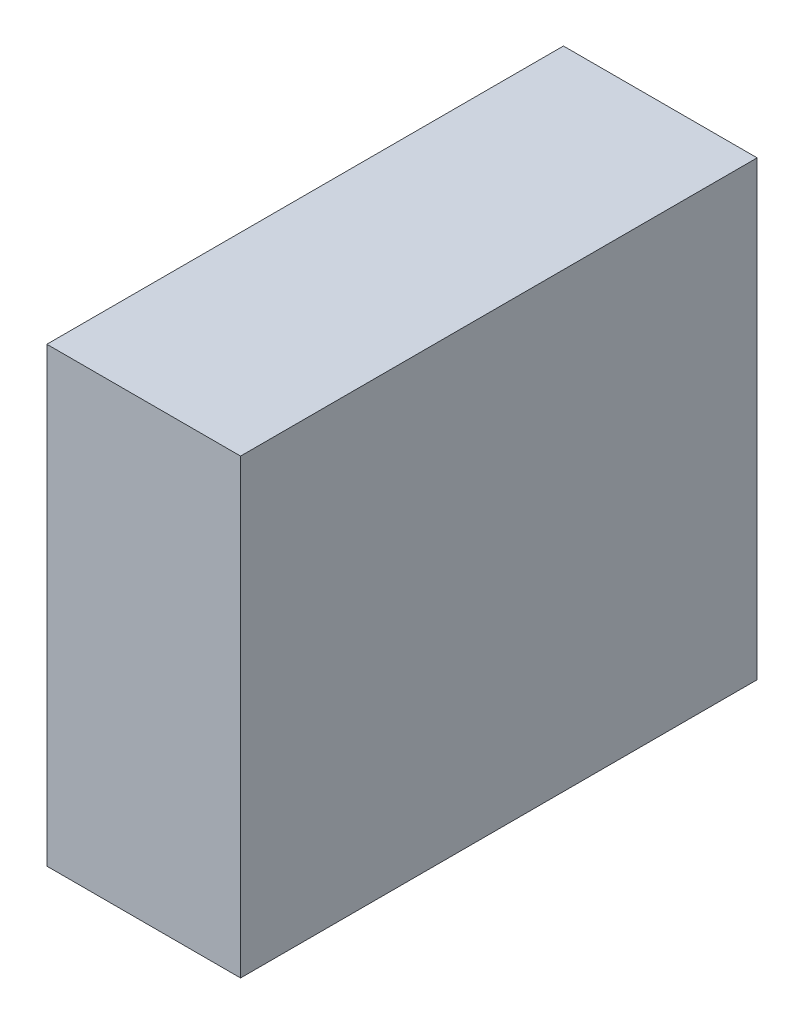
SolidWorks part; units mm, degrees
ref_plane "Front Plane" through (0, 0, 0) normal (0, 0, 1) x (1, 0, 0)
ref_plane "Top Plane" through (0, 0, 0) normal (0, 1, 0) x (1, 0, 0)
ref_plane "Right Plane" through (0, 0, 0) normal (1, 0, 0) x (0, 0, -1)
sketch "Sketch1" plane through (0, 0, 0) normal (0, 0, 1) x (1, 0, 0)
  line L1 (0, 0) -> (19.05, 0)
  line L2 (0, 0) -> (0, 44.45)
  line L3 (0, 44.45) -> (19.05, 44.45)
  line L4 (19.05, 0) -> (19.05, 44.45)
  dimension "D1" = 44.45
  dimension "D2" = 19.05
extrude "Boss-Extrude1" add sketch "Sketch1" along normal blind 50.8
